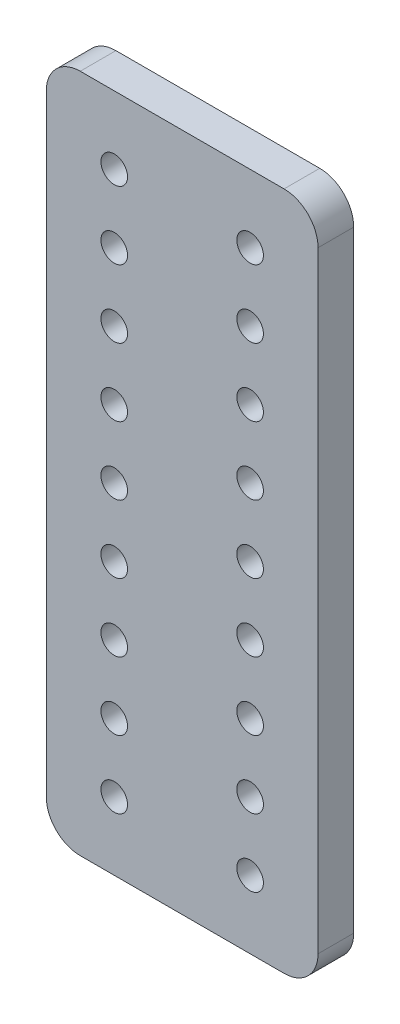
SolidWorks part; units mm, degrees
material "PET"
ref_plane "Front Plane" through (0, 0, 0) normal (0, 0, 1) x (1, 0, 0)
ref_plane "Top Plane" through (0, 0, 0) normal (0, 1, 0) x (1, 0, 0)
ref_plane "Right Plane" through (0, 0, 0) normal (1, 0, 0) x (0, 0, -1)
sketch "Sketch2" plane through (0, 0, 0) normal (0, 0, 1) x (1, 0, 0)
  line L1 (0, 0) -> (50.8, 0)
  line L2 (0, 0) -> (0, 127)
  line L3 (0, 127) -> (50.8, 127)
  line L4 (50.8, 0) -> (50.8, 127)
  dimension "D1" = 50.8
  dimension "D2" = 127
extrude "Boss-Extrude1" add sketch "Sketch2" against normal blind 6.6675
sketch "Sketch3" plane through (0, 0, 0) normal (0, 0, 1) x (1, 0, 0)
  line L0 (50.8, 127) -> (0, 127) construction
  line L1 (0, 127) -> (0, 0) construction
  circle A0 centre (12.7, 114.3) radius 2.4892
  circle A1 centre (12.7, 101.6) radius 2.4892
  circle A2 centre (12.7, 88.9) radius 2.4892
  circle A3 centre (12.7, 76.2) radius 2.4892
  circle A4 centre (12.7, 63.5) radius 2.4892
  circle A5 centre (12.7, 50.8) radius 2.4892
  circle A6 centre (12.7, 38.1) radius 2.4892
  circle A7 centre (12.7, 25.4) radius 2.4892
  circle A8 centre (12.7, 12.7) radius 2.4892
  circle A9 centre (38.1, 101.6) radius 2.4892
  circle A10 centre (38.1, 88.9) radius 2.4892
  circle A11 centre (38.1, 76.2) radius 2.4892
  circle A12 centre (38.1, 63.5) radius 2.4892
  circle A13 centre (38.1, 50.8) radius 2.4892
  circle A14 centre (38.1, 38.1) radius 2.4892
  circle A15 centre (38.1, 25.4) radius 2.4892
  circle A16 centre (38.1, 12.7) radius 2.4892
  circle A17 centre (38.1, 114.3) radius 2.4892
  dimension "D1" = 4.9784
  dimension "D2" = 12.7
  dimension "D3" = 12.7
  dimension "D4" = 9
  dimension "D5" = 2
extrude "Cut-Extrude1" cut sketch "Sketch3" against normal through all
fillet "Fillet1" radius 6.35 4 edges at (0, 0, -3.3337) (50.8, 0, -3.3337) (50.8, 127, -3.3337) (0, 127, -3.3337)
